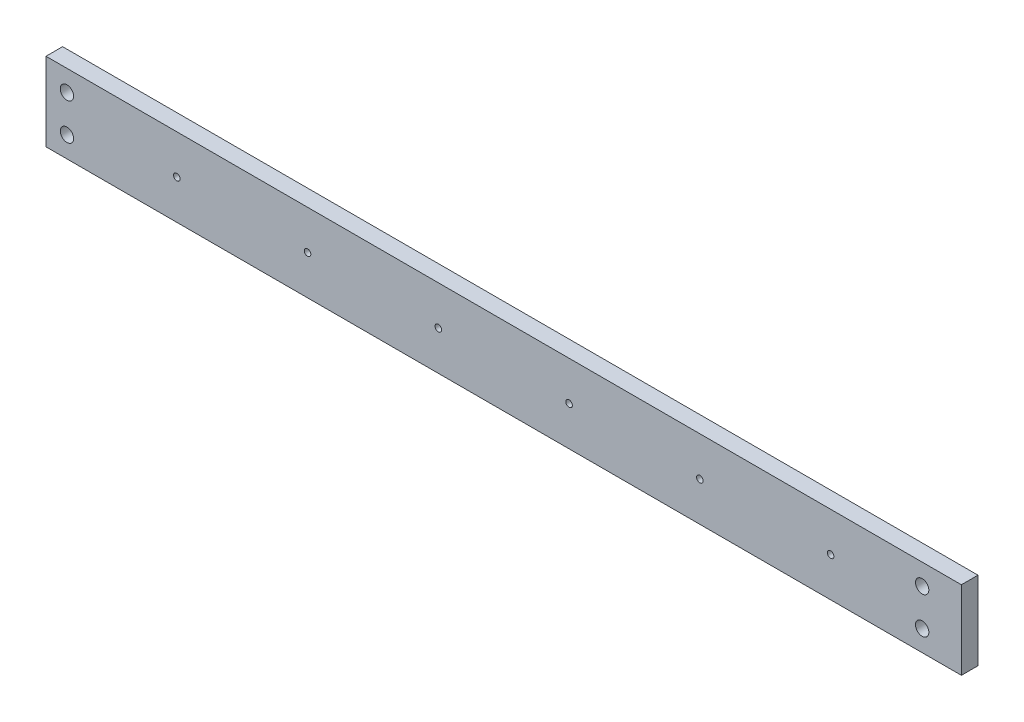
SolidWorks part; units mm, degrees
ref_plane "Front Plane" through (0, 0, 0) normal (0, 0, 1) x (1, 0, 0)
ref_plane "Top Plane" through (0, 0, 0) normal (0, 1, 0) x (1, 0, 0)
ref_plane "Right Plane" through (0, 0, 0) normal (1, 0, 0) x (0, 0, -1)
sketch "Sketch2" plane through (0, 0, 0) normal (0, 0, 1) x (1, 0, 0)
  line L1 (0, 0) -> (350, 0)
  line L2 (0, 0) -> (0, 30)
  line L3 (0, 30) -> (350, 30)
  line L4 (350, 0) -> (350, 30)
  dimension "D1" = 30
  dimension "D2" = 350
extrude "Boss-Extrude1" add sketch "Sketch2" along normal blind 6.35
sketch "Sketch3" plane through (0, 0, 6.35) normal (0, 0, 1) x (1, 0, 0)
  line L0 (8, 30) -> (8, 0) construction
  line L1 (350, 30) -> (0, 30) construction
  line L2 (0, 30) -> (0, 0) construction
  line L3 (0, 0) -> (350, 0) construction
  point P4 (8, 22)
  point P5 (8, 8)
  dimension "D1" = 8
  dimension "D2" = 8
  dimension "D3" = 8
hole_wizard "Tap Drill for 1/4-20 Tap2" positions "Sketch4" profile "Sketch5" hole size "1/4-20" standard "ANSI Inch" end condition through all
sketch "Sketch4" plane through (0, 0, 6.35) normal (0, 0, 1) x (1, 0, 0)
  point P0 (8, 22)
  point P3 (8, 8)
sketch "Sketch5" plane through (8, 22, 6.35) normal (1, 0, 0) x (0, -1, 0)
  line L0 (0, 0) -> (0, 6.35)
  line L1 (0, 6.35) -> (2.5527, 6.35)
  line L2 (2.5527, 6.35) -> (2.5527, 0)
  line L5 (2.5527, 0) -> (0, 0)
  line L11 (0, -6.35) -> (0, 107.95) construction
  dimension "Thru Hole Dia." = 5.1054
  dimension "Thru Hole Depth" = 6.35
sketch "Sketch6" plane through (0, 0, 6.35) normal (0, 0, 1) x (1, 0, 0)
  line L0 (0, 15) -> (350, 15) construction
  line L1 (0, 30) -> (0, 0) construction
  line L2 (350, 0) -> (350, 30) construction
  point P6 (50, 15)
  dimension "D1" = 50
hole_wizard "Tap Drill for M3x0.5 Tap1" positions "Sketch6" profile "Sketch7" hole size "M3x0.5" standard "ANSI Metric" end condition through all
sketch "Sketch7" plane through (50, 15, 6.35) normal (1, 0, 0) x (0, -1, 0)
  line L0 (0, 0) -> (0, 6.35)
  line L1 (0, 6.35) -> (1.25, 6.35)
  line L2 (1.25, 6.35) -> (1.25, 0)
  line L5 (1.25, 0) -> (0, 0)
  line L11 (0, -6.35) -> (0, 107.95) construction
  dimension "Thru Hole Dia." = 2.5
  dimension "Thru Hole Depth" = 6.35
pattern_linear "LPattern1" count 6 spacing 50 along (1, 0, 0) of "Tap Drill for M3x0.5 Tap1"
sketch "Sketch8" plane through (0, 0, 0) normal (0, 0, -1) x (-1, 0, 0)
  line L0 (-335, 30) -> (-335, 0) construction
  line L1 (-350, 30) -> (0, 30) construction
  line L2 (0, 0) -> (-350, 0) construction
  line L3 (-350, 0) -> (-350, 30) construction
  point P6 (-335, 15)
  point P7 (-335, 22)
  point P8 (-335, 8)
  dimension "D1" = 15
  dimension "D2" = 7
  dimension "D3" = 7
hole_wizard "Tap Drill for 1/4-20 Tap1" positions "Sketch11" profile "Sketch12" hole size "1/4-20" standard "ANSI Inch" end condition through all
sketch "Sketch11" plane through (0, 0, 0) normal (0, 0, -1) x (-1, 0, 0)
  point P0 (-335, 22)
  point P3 (-335, 8)
sketch "Sketch12" plane through (335, 22, 0) normal (1, 0, 0) x (0, 1, 0)
  line L0 (0, 0) -> (0, 6.35)
  line L1 (0, 6.35) -> (2.5527, 6.35)
  line L2 (2.5527, 6.35) -> (2.5527, 0)
  line L5 (2.5527, 0) -> (0, 0)
  line L11 (0, -6.35) -> (0, 107.95) construction
  dimension "Thru Hole Dia." = 5.1054
  dimension "Thru Hole Depth" = 6.35
